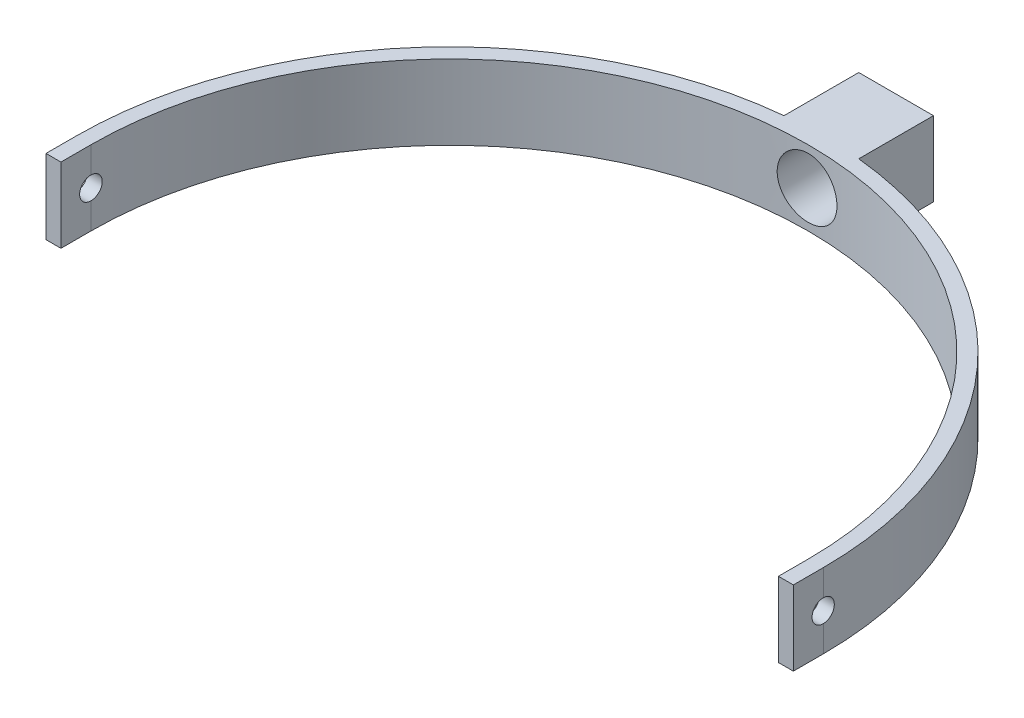
SolidWorks part; units mm, degrees
ref_plane "Front Plane" through (0, 0, 0) normal (0, 0, 1) x (1, 0, 0)
ref_plane "Top Plane" through (0, 0, 0) normal (0, 1, 0) x (1, 0, 0)
ref_plane "Right Plane" through (0, 0, 0) normal (1, 0, 0) x (0, 0, -1)
sketch "Sketch1" plane through (0, 0, 0) normal (0, 1, 0) x (1, 0, 0)
  line L0 (0, 0) -> (-250, 0) construction
  line L1 (0, 0) -> (250, 0) construction
  line L2 (0, 0) -> (0, 298.7469) construction
  line L3 (-25, 298.7469) -> (25, 298.7469)
  line L4 (-25, 298.7469) -> (-25, 248.7469)
  line L6 (-250, 0) -> (-250, -20)
  line L7 (-250, -20) -> (-240, -20)
  line L8 (-240, 0) -> (-240, -20)
  line L9 (25, 298.7469) -> (25, 248.7469)
  line L10 (240, 0) -> (240, -20)
  line L11 (240, -20) -> (250, -20)
  line L12 (250, 0) -> (250, -20)
  arc A0 (250, 0) -> (25, 248.7469) centre (0, 0) ccw
  arc A1 (240, 0) -> (-240, 0) centre (0, 0) ccw
  arc A2 (-25, 248.7469) -> (-250, 0) centre (0, 0) ccw
  dimension "D1" = 250
  dimension "D2" = 240
  dimension "D3" = 50
  dimension "D4" = 50
  dimension "D5" = 20
extrude "Boss-Extrude1" add sketch "Sketch1" along normal blind 50
sketch "Sketch2" plane through (0, 0, -298.7469) normal (0, 0, -1) x (-1, 0, 0)
  line L0 (-25, 50) -> (25, 0) construction
  line L1 (-25, 0) -> (25, 50) construction
  circle A0 centre (0, 25) radius 20
  dimension "D1" = 40
extrude "Cut-Extrude1" cut sketch "Sketch2" against normal through all contours A0
sketch "Sketch3" plane through (-250, 0, 0) normal (-1, 0, 0) x (0, 0, 1)
  line L0 (0, 50) -> (0, 0) construction
  circle A0 centre (0, 25) radius 7.5
  dimension "D1" = 15
extrude "Cut-Extrude2" cut sketch "Sketch3" against normal through all
ref_point "Point1"
ref_point "Point2"
ref_axis "Axis1" through (244.9713, 25, -0.0005) along (-1, 0, 0)
